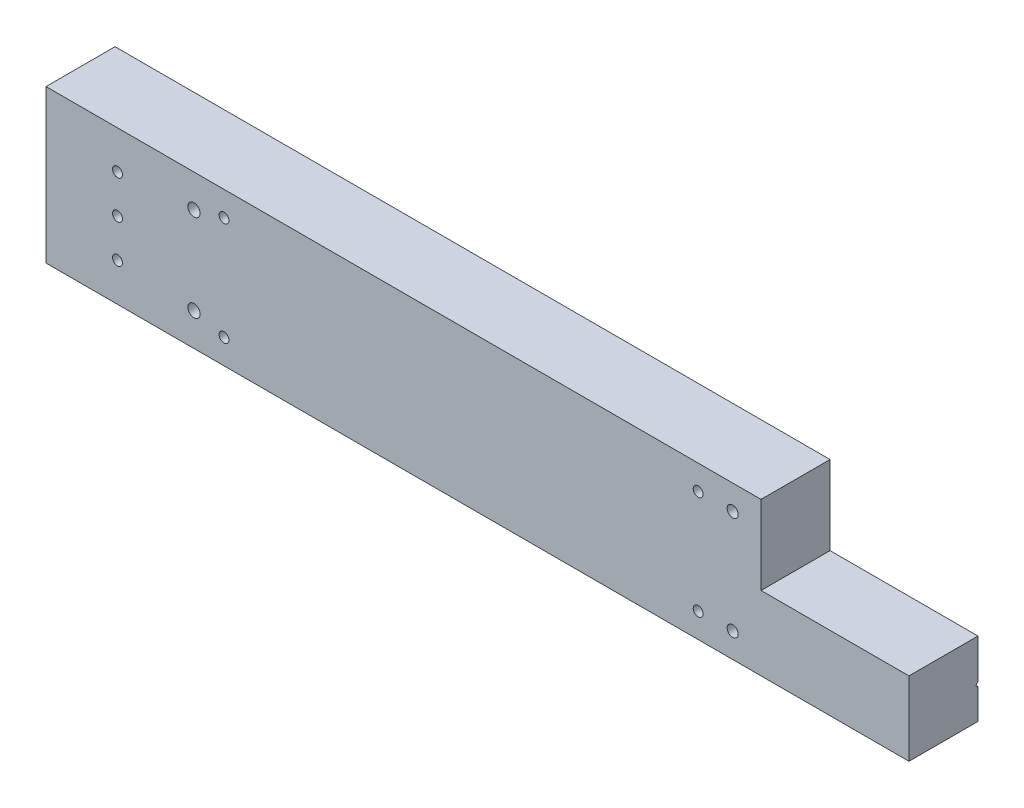
SolidWorks part; units mm, degrees
material "ABS"
ref_plane "Plano frontal" through (0, 0, 0) normal (0, 0, 1) x (1, 0, 0)
ref_plane "Plano superior" through (0, 0, 0) normal (0, 1, 0) x (1, 0, 0)
ref_plane "Plano direito" through (0, 0, 0) normal (1, 0, 0) x (0, 0, -1)
sketch "Esboço1" plane through (0, 0, 0) normal (0, 0, 1) x (1, 0, 0)
  line L0 (290, 30) -> (350, 30)
  line L1 (0, 0) -> (290, 0)
  line L2 (0, 0) -> (0, 62)
  line L3 (0, 62) -> (290, 62)
  line L4 (290, 0) -> (350, 0)
  line L5 (350, 0) -> (350, 30)
  line L16 (290, 62) -> (290, 30)
  dimension "D1" = 290
  dimension "D2" = 62
  dimension "D4" = 60
  dimension "D3" = 30
extrude "Ressalto-extrusão1" add sketch "Esboço1" along normal blind 28 contours L1 L3 L2 region at (160.9252, 29.544, 0)
sketch "Esboço2" plane through (0, 0, 0) normal (0, 0, -1) x (-1, 0, 0)
  line L0 (-290, 62) -> (-290, 30) construction
  line L2 (0, 5) -> (-350, 5)
  line L3 (-5, 5) -> (-285, 5)
  line L5 (0, 57) -> (-290, 57)
  line L6 (-5, 57) -> (-285, 57)
  line L8 (-5, 0) -> (-5, 62)
  line L9 (-5, 5) -> (-5, 57)
  line L10 (-285, 5) -> (-285, 57)
  point P2 (-195, 0)
  point P3 (-195, 80)
  dimension "D4" = 280
  dimension "D5" = 5
  dimension "D1" = 5
  dimension "D2" = 5
  dimension "D3" = 5
extrude "Corte-extrusão1" cut sketch "Esboço2" against normal blind 23
fillet "Filete6" radius 5 4 edges at (5, 5, 11.5) (5, 57, 11.5) (285, 5, 11.5) (285, 57, 11.5)
sketch "Esboço3" plane through (0, 0, 23) normal (0, 0, -1) x (-1, 0, 0)
  line L4 (-272, 30) -> (-272, 57)
  line L5 (-10, 57) -> (-280, 57) construction
  line L6 (-272, 57) -> (-280, 57)
  line L8 (-272, 30) -> (-272, 5)
  line L11 (-285, 52) -> (-285, 10)
  line L12 (-280, 5) -> (-272, 5)
  arc A0 (-280, 57) -> (-285, 52) centre (-280, 52) ccw construction
  arc A2 (-280, 57) -> (-285, 52) centre (-280, 52) ccw
  arc A3 (-280, 5) -> (-285, 10) centre (-280, 10) cw
  dimension "D1" = 13
extrude "Ressalto-extrusão2" add sketch "Esboço3" along normal blind 10
sketch "Esboço4" plane through (0, 0, 23) normal (0, 0, -1) x (-1, 0, 0)
  line L0 (-280, 5) -> (-10, 5) construction
  line L1 (-5, 10) -> (-5, 52) construction
  line L2 (-10, 57) -> (-280, 57) construction
  line L7 (-272, 5) -> (-10, 5) construction
  circle A0 centre (-72.2, 10) radius 2
  circle A1 centre (-72.2, 52) radius 2
  circle A2 centre (-244, 11) radius 2.5
  circle A3 centre (-244, 51) radius 2.5
  dimension "D4" = 4
  dimension "D5" = 4
  dimension "D3" = 5
  dimension "D8" = 5
  dimension "D1" = 5
  dimension "D2" = 5
  dimension "D6" = 6
  dimension "D7" = 6
  dimension "D9" = 67.2
  dimension "D10" = 67.2
extrude "Corte-extrusão3" cut sketch "Esboço4" against normal through all contours A1 | A0
sketch "Esboço5" plane through (0, 0, 23) normal (0, 0, -1) x (-1, 0, 0)
  line L0 (-285, 52) -> (-285, 10) construction
  line L4 (-10, 57) -> (-272, 57) construction
  line L5 (-272, 5) -> (-10, 5) construction
  circle A0 centre (-264.5, 10) radius 2
  circle A1 centre (-264.5, 52) radius 2
  dimension "D4" = 4
  dimension "D5" = 4
  dimension "D1" = 20.5
  dimension "D2" = 5
  dimension "D3" = 5
  dimension "D6" = 20.5
extrude "Corte-extrusão4" cut sketch "Esboço5" against normal through all contours A1 | A0 region at (264.5, 10, 23) region at (264.5, 52, 23)
sketch "Esboço6" plane through (0, 0, 13) normal (0, 0, -1) x (-1, 0, 0)
  line L0 (-285, 52) -> (-285, 10) construction
  line L1 (-280, 5) -> (-10, 5) construction
  line L2 (-272, 57) -> (-280, 57) construction
  circle A0 centre (-278.5, 10) radius 2.25
  circle A1 centre (-278.5, 52) radius 2.25
  dimension "D3" = 4.5
  dimension "D4" = 4.5
  dimension "D1" = 6.5
  dimension "D2" = 5
  dimension "D5" = 5
  dimension "D6" = 6.5
extrude "Corte-extrusão5" cut sketch "Esboço6" against normal through all contours A1 | A0
sketch "Esboço7" plane through (0, 0, 23) normal (0, 0, -1) x (-1, 0, 0)
  line L0 (-10, 57) -> (-272, 57) construction
  line L2 (-272, 5) -> (-10, 5) construction
  line L3 (-5, 10) -> (-5, 52) construction
  circle A0 centre (-60, 48.7) radius 2.5
  circle A1 centre (-60, 13.3) radius 2.5
  dimension "D1" = 5
  dimension "D4" = 5
  dimension "D2" = 8.3
  dimension "D3" = 8.3
  dimension "D5" = 55
  dimension "D6" = 55
extrude "Corte-extrusão6" cut sketch "Esboço7" against normal blind 10 contours A1 | A0
sketch "Esboço13" plane through (0, 0, 23) normal (0, 0, -1) x (-1, 0, 0)
  circle A6 centre (-29, 46.5) radius 2
  circle A7 centre (-29, 31) radius 2
  circle A8 centre (-29, 15.5) radius 2
  dimension "D15" = 4
  dimension "D16" = 4
  dimension "D17" = 4
extrude "Corte-extrusão12" cut sketch "Esboço13" against normal through all
sketch "Esboço15" plane through (0, 0, 0) normal (0, 0, -1) x (-1, 0, 0)
  line L0 (-280, 8) -> (-310, 8)
  line L6 (-310, 8) -> (-310, 18)
  line L8 (-310, 18) -> (-280, 18)
  line L22 (-280, 8) -> (-280, 18)
extrude "Corte-extrusão13" cut sketch "Esboço15" against normal blind 4
sketch "Esboço16" plane through (310, 0, 0) normal (-1, 0, 0) x (0, 0, 1)
  line L0 (0, 18) -> (0, 8) construction
  circle A0 centre (0, 13) radius 0.75
  dimension "D1" = 1.5
extrude "Corte-extrusão14" cut sketch "Esboço16" against normal through all
fillet "Filete7" radius 5 2 edges at (310, 18, 2) (310, 8, 2)
sketch "Esboço17" plane through (0, 0, 0) normal (0, 0, -1) x (-1, 0, 0)
  line L0 (-305, 8) -> (-284.5826, 8) construction
  line L1 (-285, 18) -> (-305, 18) construction
  circle A0 centre (-294.7913, 4) radius 2
  circle A1 centre (-295, 22) radius 2
  dimension "D1" = 4
  dimension "D2" = 4
  dimension "D3" = 4
  dimension "D4" = 4
extrude "Corte-extrusão15" cut sketch "Esboço17" against normal blind 10
